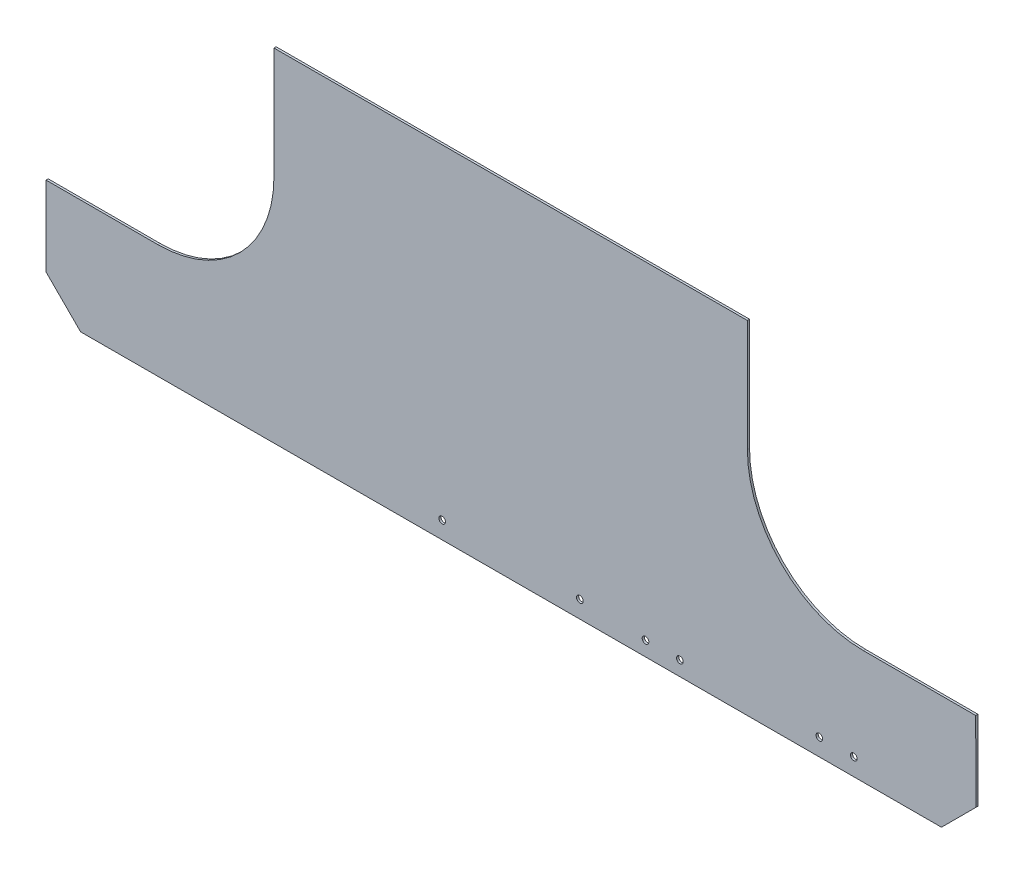
SolidWorks part; units mm, degrees
material "Perspex (TM) GS Acrylic Cast Sheet"
ref_plane "Front Plane" through (0, 0, 0) normal (0, 0, 1) x (1, 0, 0)
ref_plane "Top Plane" through (0, 0, 0) normal (0, 1, 0) x (1, 0, 0)
ref_plane "Right Plane" through (0, 0, 0) normal (1, 0, 0) x (0, 0, -1)
sketch "Sketch1" plane through (0, 0, 0) normal (0, 0, 1) x (1, 0, 0)
  line L1 (-457.2, -304.8) -> (457.2, -304.8)
  line L2 (-457.2, -304.8) -> (-457.2, 304.8)
  line L3 (-457.2, 304.8) -> (457.2, 304.8)
  line L4 (457.2, -304.8) -> (457.2, 304.8)
  line L5 (0, 304.8) -> (0, -304.8) construction
  line L6 (-457.2, 0) -> (457.2, 0) construction
  point P0 (0, 0)
  point P4 (-320.04, 0)
  point P5 (320.04, 0)
  point P6 (0, 213.36)
  point P7 (0, -213.36)
  dimension "Length" = 914.4
  dimension "Width" = 609.6
  dimension "Break" = 137.16
  dimension "D2" = 137.16
  dimension "D1" = 91.44
  dimension "D3" = 91.44
sketch "Sketch2" plane through (0, 0, 0) normal (1, 0, 0) x (0, 0, -1)
  line L0 (-0.7938, -304.8) -> (0.7938, -304.8)
  dimension "Thickness" = 1.5875
sketch "Sketch3" plane through (0, 0, 0) normal (0, 0, 1) x (1, 0, 0)
  line L0 (-457.2, -304.8) -> (-457.2, 304.8) construction
  line L1 (-457.2, -304.8) -> (457.2, -304.8) construction
  line L2 (457.2, -304.8) -> (457.2, 304.8) construction
  line L3 (-457.2, 304.8) -> (457.2, 304.8) construction
  line L4 (-457.2, -304.8) -> (-457.2, 304.8)
  line L5 (-457.2, -304.8) -> (457.2, -304.8)
  line L6 (457.2, -304.8) -> (457.2, 304.8)
  line L7 (-457.2, 304.8) -> (457.2, 304.8)
extrude "Boss-Extrude1" add sketch "Sketch3" along normal mid plane 1.5875
sketch "Sketch4" plane through (0, 0, 0.7937) normal (0, 0, 1) x (1, 0, 0)
  line L1 (-362.5066, 0.4474) -> (318.2125, 1.5649)
  line L2 (-339.2322, -251.9272) -> (-364.674, -226.4854)
  line L5 (-363.9625, -659.9558) -> (-365.0466, 0.4433) construction
  line L12 (-364.674, -226.4854) -> (-365.0424, -2.0967)
  line L15 (-339.2322, -251.9272) -> (295.7669, -250.8848)
  line L26 (295.7669, -250.8848) -> (321.1253, -225.5264)
  line L27 (320.7942, -23.8309) -> (321.8783, -684.23) construction
  line L28 (321.1253, -225.5264) -> (320.7567, -0.9709)
  arc A2 (318.2125, 1.5649) -> (320.7567, -0.9709) centre (318.2167, -0.9751) cw
  arc A3 (-362.5066, 0.4474) -> (-365.0424, -2.0967) centre (-362.5024, -2.0926) ccw
  point P12 (320.7525, 1.5691)
  point P15 (-365.0466, 0.4433)
  dimension "D1" = 2.54
  dimension "D2" = 2.54
extrude "Cut-Extrude1" cut sketch "Sketch4" against normal blind 2.54 flip side to cut
sketch "Sketch12" plane through (0, 0, -0.7937) normal (0, 0, -1) x (-1, 0, 0)
  line L19 (196.6362, 20.4048) -> (384.7638, 20.0959)
  line L20 (384.4556, -167.696) -> (384.7638, 20.0959)
  line L21 (282.2232, -167.696) -> (384.4556, -167.696)
  line L22 (196.6362, -81.8669) -> (196.6362, 20.4048)
  arc A3 (282.2232, -167.696) -> (196.6362, -81.8669) centre (282.4657, -81.8669) cw
sketch "Sketch9" plane through (0, 0, 0.7937) normal (0, 0, 1) x (1, 0, 0)
  point P0 (-365.5467, -279.4147)
  point P1 (-339.7911, -292.1147)
  point P3 (-314.3911, -292.1147)
  point P5 (-365.5467, -229.8463)
  point P15 (270.1645, -292.1147)
  point P17 (295.5645, -292.1147)
  point P19 (321.3201, -279.4147)
  point P21 (320.9651, -229.8463)
  point P23 (-219.4967, -52.0463)
  point P25 (174.9151, -52.0463)
hole_wizard "#10 (0.1935) Diameter Hole1" positions "Sketch10" profile "Sketch11" hole size "#10" standard "ANSI Inch" end condition through all
sketch "Sketch10" plane through (0, 0, 0.7937) normal (0, 0, 1) x (1, 0, 0)
  point P0 (-314.3911, -292.1147)
  point P3 (-339.7911, -292.1147)
  point P6 (-365.5467, -279.4147)
  point P21 (295.5645, -292.1147)
  point P24 (270.1645, -292.1147)
  point P27 (321.3201, -279.4147)
  point P31 (174.9151, -52.0463)
  point P34 (-219.4967, -52.0463)
  point P37 (77.4365, -240.4866)
  point P40 (102.8365, -240.4449)
  point P43 (205.7032, -238.3326)
  point P46 (231.1032, -238.2909)
  point P49 (-72.5534, -238.7894)
  point P52 (29.0464, -238.6226)
sketch "Sketch11" plane through (-314.3911, -292.1147, 0.7937) normal (1, 0, 0) x (0, -1, 0)
  line L0 (0, 0) -> (0, 1.5875)
  line L1 (0, 1.5875) -> (2.4574, 1.5875)
  line L2 (2.4574, 1.5875) -> (2.4574, 0)
  line L5 (2.4574, 0) -> (0, 0)
  line L11 (0, -6.35) -> (0, 107.95) construction
  dimension "Thru Hole Dia." = 4.9149
  dimension "Thru Hole Depth" = 1.5875
sketch "Sketch13" plane through (0, 0, -0.7937) normal (0, 0, -1) x (-1, 0, 0)
  line L10 (-152.6132, -81.2206) -> (-152.6132, 23.5181)
  line L11 (-152.6132, 23.5181) -> (-342.941, 23.8305)
  line L12 (-343.254, -166.8413) -> (-342.941, 23.8305)
  line L13 (-238.2339, -166.8413) -> (-343.254, -166.8413)
  arc A3 (-238.2339, -166.8413) -> (-152.6132, -81.2206) centre (-238.2339, -81.2206) ccw
extrude "Cut-Extrude5" cut sketch "Sketch13" against normal blind 2.54
extrude "Cut-Extrude6" cut sketch "Sketch12" against normal blind 2.54
equation "\"D1@Boss-Extrude1\"=\"thickness@sketch2\""
equation "\"Break@Sketch1\" = \"Length@Sketch1\" * 0.15"
equation "\"D2@Sketch1\" = \"Break@Sketch1\""
equation "\"D1@Sketch1\"=\"Width@Sketch1\"*0.15"
equation "\"D3@Sketch1\"=\"D1@Sketch1\""
